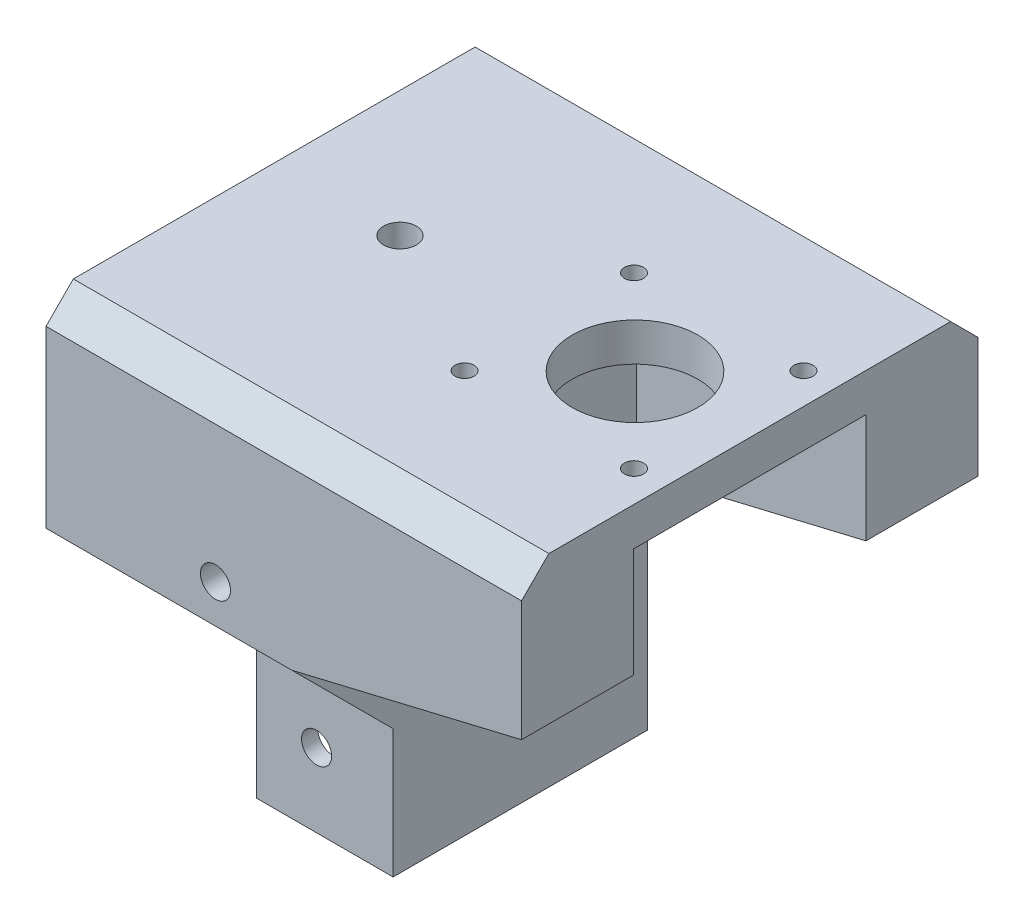
SolidWorks part; units mm, degrees
ref_plane "Front Plane" through (0, 0, 0) normal (0, 0, 1) x (1, 0, 0)
ref_plane "Top Plane" through (0, 0, 0) normal (0, 1, 0) x (1, 0, 0)
ref_plane "Right Plane" through (0, 0, 0) normal (1, 0, 0) x (0, 0, -1)
sketch "Sketch1" plane through (0, 0, 0) normal (0, 1, 0) x (1, 0, 0)
  line L0 (0, 0) -> (0, 40.5)
  line L1 (0, 40.5) -> (3, 40.5)
  line L2 (3, 40.5) -> (3, -3)
  line L3 (3, -3) -> (-22, -3)
  line L4 (-22, -3) -> (-22, 0)
  line L5 (-22, 0) -> (0, 0)
  dimension "D1" = 22
  dimension "D2" = 40.5
  dimension "D3" = 3
  dimension "D4" = 3
extrude "Boss-Extrude1" add sketch "Sketch1" along normal blind 75
sketch "Sketch2" plane through (0, 75, 0) normal (0, 1, 0) x (1, 0, 0)
  line L0 (3, 40.5) -> (0, 40.5) construction
  line L2 (-19.0018, 20.25) -> (0, 20.25) construction
  line L3 (-0.0018, 40.5) -> (-42.0018, 40.5)
  line L4 (-42.0018, 0) -> (-42.0018, 40.5)
  line L5 (-0.0018, 40.5) -> (3, 40.5)
  line L6 (3, 40.5) -> (3, -3)
  line L7 (3, -3) -> (-42.0018, -3)
  line L8 (-42.0018, -3) -> (-42.0018, 0)
  line L9 (0, 40.5) -> (0, 0) construction
  circle A0 centre (-19.0018, 20.25) radius 3
  dimension "D3" = 6
  dimension "D1" = 42
  dimension "D2" = 19
sketch "Sketch4" plane through (3, 0, 0) normal (1, 0, 0) x (0, 0, -1)
  line L2 (40.5, 75) -> (0, 75) construction
  line L3 (-3, 75) -> (40.5, 75) construction
  circle A0 centre (20.25, 27) radius 3
  point P6 (20.25, 75)
  dimension "D1" = 6
  dimension "D2" = 0
  dimension "D3" = 48
extrude "Cut-Extrude1" cut sketch "Sketch4" against normal blind 3
extrude "Boss-Extrude2" add sketch "Sketch2" against normal blind 3 and the other way blind 4
sketch "Sketch8" plane through (0, 0, 3) normal (0, 0, 1) x (1, 0, 0)
  line L0 (-22, 72) -> (-22, 0) construction
  line L1 (-42.0018, 72) -> (-22, 72)
  line L2 (-42.0018, 72) -> (-42.0018, 42)
  line L3 (-42.0018, 42) -> (-22, 42)
  line L4 (-22, 72) -> (-22, 42)
  dimension "D1" = 30
extrude "Boss-Extrude6" add sketch "Sketch8" against normal blind 3
sketch "Sketch9" plane through (0, 0, -40.5) normal (0, 0, -1) x (-1, 0, 0)
  line L2 (42.0018, 72) -> (42.0018, 42)
  line L3 (42.0018, 42) -> (2.5, 42)
  line L4 (2.5, 72) -> (2.5, 42)
  line L6 (-3, 79) -> (-3, 0)
  line L7 (-3, 0) -> (0, 0)
  line L8 (0, 0) -> (0, 72)
  line L9 (0, 72) -> (42.0018, 72)
  line L10 (42.0018, 72) -> (42.0018, 79)
  line L11 (42.0018, 79) -> (-3, 79)
  line L12 (-3, 79) -> (-3, 0)
  line L13 (-3, 0) -> (0, 0)
  line L14 (0, 0) -> (0, 72)
  line L15 (0, 72) -> (42.0018, 72)
  line L16 (42.0018, 72) -> (42.0018, 79)
  line L17 (42.0018, 79) -> (-3, 79)
  line M9 (-3, 79) -> (-3, 0)
  line M10 (-3, 0) -> (0, 0)
  line M11 (0, 0) -> (0, 72)
  line M12 (0, 72) -> (42.0018, 72)
  line M13 (42.0018, 72) -> (42.0018, 79)
  line M14 (42.0018, 79) -> (-3, 79)
  dimension "D2" = 30
  dimension "D3" = 2.5
  dimension "D1" = 0
extrude "Boss-Extrude7" add sketch "Sketch9" along normal blind 3 contours M14 M9 M10 M11 M12 M13 | L4 L3 L2 M12 region at (-22.2509, 57, -40.5) region at (-22.2509, 72.9092, -40.5)
sketch "Sketch10" plane through (-42.0018, 0, 0) normal (-1, 0, 0) x (0, 0, 1)
  line L0 (-40.5, 72) -> (0, 72) construction
  line L1 (3, 79) -> (16.5, 79)
  line L2 (21.5, 74) -> (21.5, 42)
  line L3 (21.5, 42) -> (3, 42)
  line L4 (3, 42) -> (3, 79)
  line L5 (16.5, 79) -> (21.5, 74)
  circle A0 centre (11.5, 62) radius 4.05
  point P4 (-20.25, 72)
  point P6 (21.5, 79)
  dimension "D1" = 8.1
  dimension "D2" = 31.75
  dimension "D3" = 18.5
extrude "Boss-Extrude8" add sketch "Sketch10" against normal up to surface (45.0018 mm away) up to face at (3, 39.5, -20.25)
sketch "Sketch11" plane through (3, 0, 0) normal (1, 0, 0) x (0, 0, -1)
  line L0 (40.5, 72) -> (0, 72) construction
  line L1 (-1, 72) -> (41.5, 72)
  line L2 (41.5, 72) -> (41.5, 42)
  line L4 (-1, 72) -> (-1, 42)
  line L5 (-1, 42) -> (-3, 42)
  line L6 (41.5, 42) -> (43.5, 42)
  line L7 (43.5, 79) -> (-16.5, 79)
  line L11 (-3, 42) -> (-3, 0)
  line L12 (-3, 0) -> (43.5, 0)
  line L13 (43.5, 0) -> (43.5, 79)
  line L14 (43.5, 79) -> (-16.5, 79)
  line L18 (-3, 42) -> (-3, 0)
  line L19 (-3, 0) -> (43.5, 0)
  line L20 (43.5, 0) -> (43.5, 79)
  line L22 (-16.5, 79) -> (-21.5, 74)
  line L23 (-16.5, 79) -> (-21.5, 74)
  line L24 (-21.5, 74) -> (-21.5, 42)
  line L25 (-21.5, 74) -> (-21.5, 42)
  line L26 (-21.5, 42) -> (-3, 42)
  line L27 (-21.5, 42) -> (-3, 42)
  point P10 (20.25, 72)
  point P13 (20.25, 72)
  line M11 (43.5, 79) -> (-16.5, 79)
  line M12 (-16.5, 79) -> (-21.5, 74)
  line M13 (-21.5, 74) -> (-21.5, 42)
  line M14 (-21.5, 42) -> (-3, 42)
  line M17 (43.5, 0) -> (43.5, 79)
  circle M19 centre (-11.5, 62) radius 4.05
  dimension "D2" = 42.5
  dimension "D3" = 0
  dimension "D4" = 7
  dimension "D1" = 0
extrude "Boss-Extrude9" add sketch "Sketch11" along normal blind 42 contours L2 L6 L5 L4 L1 M17 M11 M12 M13 M14 M19 region at (3, 57, 1.7479)
sketch "Sketch12" plane through (0, 72, 0) normal (0, -1, 0) x (1, 0, 0)
  line L0 (45, 1) -> (3, -41.5) construction
  line L1 (39.3176, -4.75) -> (8.3176, -4.75) construction
  line L2 (45, 1) -> (45, -41.5) construction
  line L3 (24, -20.25) -> (28.9777, -20.25) construction
  circle A0 centre (24, -20.25) radius 11.5
  circle A1 centre (39.3176, -4.75) radius 1.75
  circle A2 centre (8.3176, -4.75) radius 1.75
  circle A3 centre (8.3176, -35.75) radius 1.75
  circle A4 centre (39.3176, -35.75) radius 1.75
  dimension "D1" = 23
  dimension "D3" = 3.5
  dimension "D2" = 31
  dimension "D4" = 15.5
ref_plane "Plane1" through (0, 0, -20.25) normal (0, 0, 1) x (1, 0, 0)
mirror "Mirror3" about plane through (0, 0, -20.25) normal (0, 0, 1) of "Boss-Extrude8"
sketch "Sketch13" plane through (3, 0, 0) normal (1, 0, 0) x (0, 0, -1)
  line L5 (43.5, 42) -> (62, 42)
  line L6 (62, 42) -> (62, 74)
  line L7 (62, 74) -> (57, 79)
  line L8 (57, 79) -> (43.5, 79)
  line L9 (43.5, 79) -> (43.5, 42)
  line L10 (43.5, 42) -> (62, 42)
  line L11 (62, 42) -> (62, 74)
  line L12 (62, 74) -> (57, 79)
  line L13 (57, 79) -> (43.5, 79)
  line L14 (43.5, 79) -> (43.5, 42)
  circle A0 centre (52, 62) radius 4.05
  dimension "D1" = 0
extrude "Cut-Extrude2" cut sketch "Sketch12" against normal blind 42
extrude "Cut-Extrude3" cut sketch "Sketch13" against normal up to surface (5.5 mm away) up to face at (-2.5, 57, -42)
sketch "Sketch14" plane through (0, 79, 0) normal (0, 1, 0) x (1, 0, 0)
  line L0 (-2.5, 62) -> (-42.0018, 62) construction
  line L1 (-2.5, 43.5) -> (45, 43.5)
  line L2 (-2.5, 43.5) -> (-2.5, 62)
  line L3 (-2.5, 62) -> (45, 62)
  line L4 (45, 43.5) -> (45, 62)
  line L5 (45, 43.5) -> (45, -16.5) construction
extrude "Boss-Extrude11" add sketch "Sketch14" against normal up to surface (7 mm away) up to face at (39.3176, 72, -6.5)
chamfer "Chamfer1" distance 5 angle 45 1 edges at (21.25, 79, -62)
ref_plane "Plane2" through (45, 42, -43.5) normal (0, 0, -1) x (-1, 0, 0)
sketch "Sketch17" plane through (0, 72, 0) normal (0, -1, 0) x (-1, 0, 0)
  line L1 (0, 43.5) -> (-45, 43.5)
  line L2 (0, 43.5) -> (0, 62)
  line L3 (0, 62) -> (-45, 62)
  line L4 (-45, 43.5) -> (-45, 62)
extrude "Boss-Extrude12" add sketch "Sketch17" along normal up to surface (30 mm away) up to face at (24, 42, -42.5)
sketch "Sketch18" plane through (0, 0, 1) normal (0, 0, -1) x (-1, 0, 0)
  line L0 (-45, 52) -> (-45, 42)
  line L1 (-45, 72) -> (-45, 42) construction
  line L2 (-45, 42) -> (-3, 42)
  line L3 (-3, 42) -> (-45, 52)
  dimension "D1" = 20
extrude "Cut-Extrude5" cut sketch "Sketch18" against normal through all both and the other way through all
sketch "Sketch19" plane through (0, 0, 0) normal (0, 0, -1) x (-1, 0, 0)
  line L2 (11, 100.5) -> (11, 49) construction
  line L3 (11, 49) -> (11, 72) construction
  line L4 (0, 72) -> (42.0018, 72) construction
  line L5 (11, 49) -> (11, 13.5) construction
  circle A0 centre (11, 49) radius 2.75
  circle A1 centre (11, 13.5) radius 2.75
  dimension "D3" = 5.5
  dimension "D4" = 5.5
  dimension "D1" = 23
  dimension "D2" = 58.5
extrude "Cut-Extrude6" cut sketch "Sketch19" against normal blind 22
sketch "Sketch20" plane through (45, 0, 0) normal (1, 0, 0) x (0, 0, -1)
  circle A0 centre (-11.5, 62) radius 4.05
extrude "Boss-Extrude13" add sketch "Sketch20" against normal blind 22
sketch "Sketch22" plane through (-42.0018, 0, 0) normal (-1, 0, 0) x (0, 0, 1)
  line L0 (-52, 62) -> (-52, 52)
  line L1 (11.5, 62) -> (11.5, 52)
  dimension "D1" = 10
extrude "Cut-Extrude-Thin1" cut sketch "Sketch22" against normal blind 51 thin thin type mid plane wall 1
chamfer "Chamfer2" distance 18.5 angle 45 1 edges at (-9.5, 42, 3)
